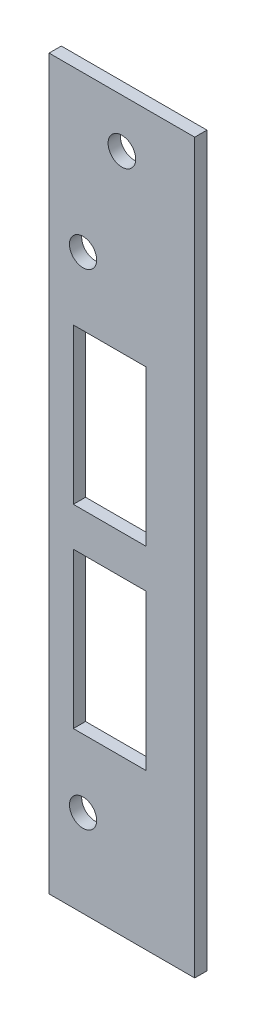
SolidWorks part; units mm, degrees
ref_plane "Front" through (0, 0, 0) normal (0, 0, 1) x (1, 0, 0)
ref_plane "Top" through (0, 0, 0) normal (0, 1, 0) x (1, 0, 0)
ref_plane "Right" through (0, 0, 0) normal (1, 0, 0) x (0, 0, -1)
sketch "Sketch1" plane through (0, 0, 0) normal (0, 0, 1) x (1, 0, 0)
  line L1 (0, 0) -> (19.05, 0)
  line L2 (0, 0) -> (0, -95.25)
  line L3 (0, -95.25) -> (19.05, -95.25)
  line L4 (19.05, 0) -> (19.05, -95.25)
  dimension "D1" = 19.05
  dimension "D2" = 95.25
extrude "Extrude1" add sketch "Sketch1" along normal blind 1.6002
sketch "Sketch2" plane through (0, 0, 1.6002) normal (0, 0, 1) x (1, 0, 0)
  line L0 (19.05, -95.25) -> (19.05, 0) construction
  line L1 (19.05, 0) -> (0, 0) construction
  circle A0 centre (9.525, -6.35) radius 1.8034
  dimension "D1" = 3.6068
  dimension "D3" = 9.525
  dimension "D4" = 6.35
extrude "Cut-Extrude1" cut sketch "Sketch2" against normal blind 1.6002
sketch "Sketch3" plane through (0, 0, 1.6002) normal (0, 0, 1) x (1, 0, 0)
  line L0 (0, -95.25) -> (19.05, -95.25) construction
  line L2 (0, 0) -> (0, -95.25) construction
  circle A0 centre (4.445, -20.32) radius 1.778
  circle A1 centre (4.445, -83.82) radius 1.778
  dimension "D1" = 3.556
  dimension "D2" = 3.556
  dimension "D3" = 11.43
  dimension "D4" = 4.445
  dimension "D5" = 63.5
extrude "Cut-Extrude2" cut sketch "Sketch3" against normal blind 2.54
sketch "Sketch4" plane through (0, 0, 1.6002) normal (0, 0, 1) x (1, 0, 0)
  line L1 (3.175, -29.21) -> (12.7, -29.21)
  line L2 (3.175, -29.21) -> (3.175, -49.53)
  line L3 (3.175, -49.53) -> (12.7, -49.53)
  line L4 (12.7, -29.21) -> (12.7, -49.53)
  line L5 (3.175, -54.61) -> (12.7, -54.61)
  line L6 (3.175, -54.61) -> (3.175, -74.93)
  line L7 (3.175, -74.93) -> (12.7, -74.93)
  line L8 (12.7, -54.61) -> (12.7, -74.93)
  line L9 (0, 0) -> (0, -95.25) construction
  circle A1 centre (4.445, -83.82) radius 1.778 construction
  circle A2 centre (4.445, -20.32) radius 1.778 construction
  dimension "D3" = 9.525
  dimension "D2" = 8.89
  dimension "D7" = 8.89
  dimension "D1" = 20.32
  dimension "D4" = 3.175
  dimension "D5" = 20.32
  dimension "D6" = 9.525
  dimension "D8" = 3.175
extrude "Fiber Holes" cut sketch "Sketch4" against normal blind 2.54
